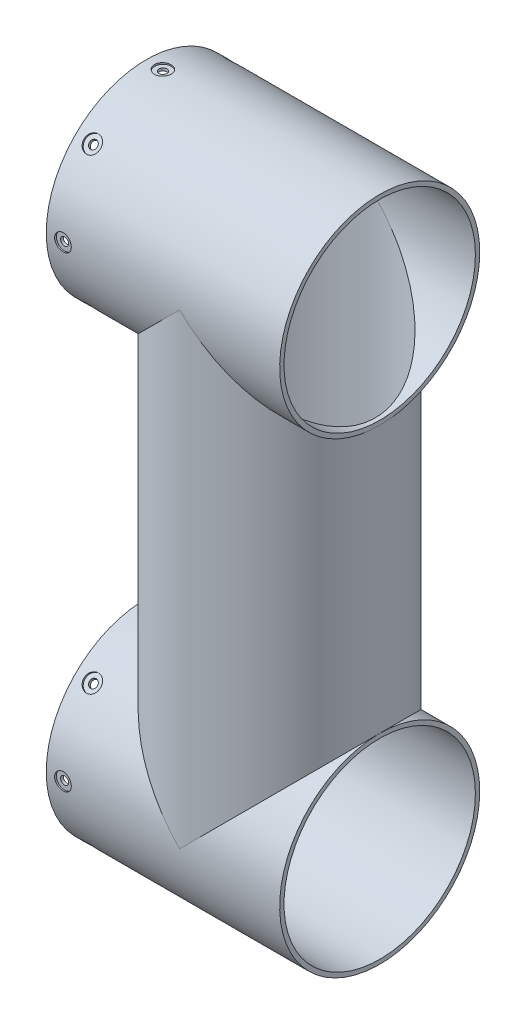
SolidWorks part; units mm, degrees
ref_plane "정면" through (0, 0, 0) normal (0, 0, 1) x (1, 0, 0)
ref_plane "윗면" through (0, 0, 0) normal (0, 1, 0) x (1, 0, 0)
ref_plane "우측면" through (0, 0, 0) normal (1, 0, 0) x (0, 0, -1)
sketch "스케치1" plane through (0, 0, 0) normal (0, 1, 0) x (1, 0, 0)
  circle A0 centre (0, 0) radius 30
  dimension "D1" = 60
extrude "보스-돌출1" add sketch "스케치1" along normal blind 140
sketch "스케치2" plane through (0, 0, 0) normal (1, 0, 0) x (0, 0, -1)
  circle A0 centre (0, 0) radius 30
extrude "보스-돌출2" add sketch "스케치2" along normal blind 30 and the other way blind 40
sketch "스케치3" plane through (30, 0, 0) normal (1, 0, 0) x (0, 0, -1)
  circle A0 centre (0, 0) radius 28.7
  circle A1 centre (0, 0) radius 30 construction
  dimension "D1" = 1.3
extrude "컷-돌출1" cut sketch "스케치3" against normal through all
sketch "스케치4" plane through (0, 140, 0) normal (0, 1, 0) x (1, 0, 0)
  circle A0 centre (0, 0) radius 28.7
  circle A1 centre (0, 0) radius 30 construction
  dimension "D1" = 1.3
ref_plane "평면1" through (0, 0, 30) normal (0, 0, 1) x (1, 0, 0)
sketch "스케치5" plane through (0, 0, 30) normal (0, 0, 1) x (1, 0, 0)
  line L0 (-40, 30) -> (-40, -30) construction
  point P0 (-35, 0)
  dimension "D1" = 5
hole_wizard "M2 남비 머리 나사용 카운터보어1" positions "스케치6" profile "스케치7" counterbore size "M2" standard "ISO"
sketch "스케치6" plane through (0, 0, 30) normal (0, 0, 1) x (1, 0, 0)
  point P0 (-35, 0)
sketch "스케치7" plane through (-35, 0, 30) normal (1, 0, 0) x (0, -1, 0)
  line L0 (0, 0) -> (0, 10.721)
  line L1 (0, 10.721) -> (1.2, 10)
  line L2 (1.2, 10) -> (1.2, 0.5)
  line L3 (1.2, 0.5) -> (2.5, 0.5)
  line L4 (2.5, 0.5) -> (2.5, 0)
  line L5 (2.5, 0) -> (0, 0)
  line L10 (0, 10.721) -> (-1.2, 10) construction
  line L11 (0, -6.35) -> (0, 107.95) construction
  dimension "구멍 지름" = 2.4
  dimension "구멍 깊이" = 10
  dimension "카운터보어 지름" = 5
  dimension "카운터보어 깊이" = 0.5
  dimension "드릴 각도" = 118
pattern_circular "원형 패턴1" count 8 over 360 about axis through (-40, 0, 0) along (1, 0, 0) of "M2 남비 머리 나사용 카운터보어1"
ref_plane "평면2" through (0, 70, 0) normal (0, 1, 0) x (1, 0, 0)
mirror "대칭 복사2" about plane through (0, 70, 0) normal (0, 1, 0) of "컷-돌출1", "보스-돌출2", "M2 남비 머리 나사용 카운터보어1", "원형 패턴1"
extrude "컷-돌출2" cut sketch "스케치4" against normal blind 140
